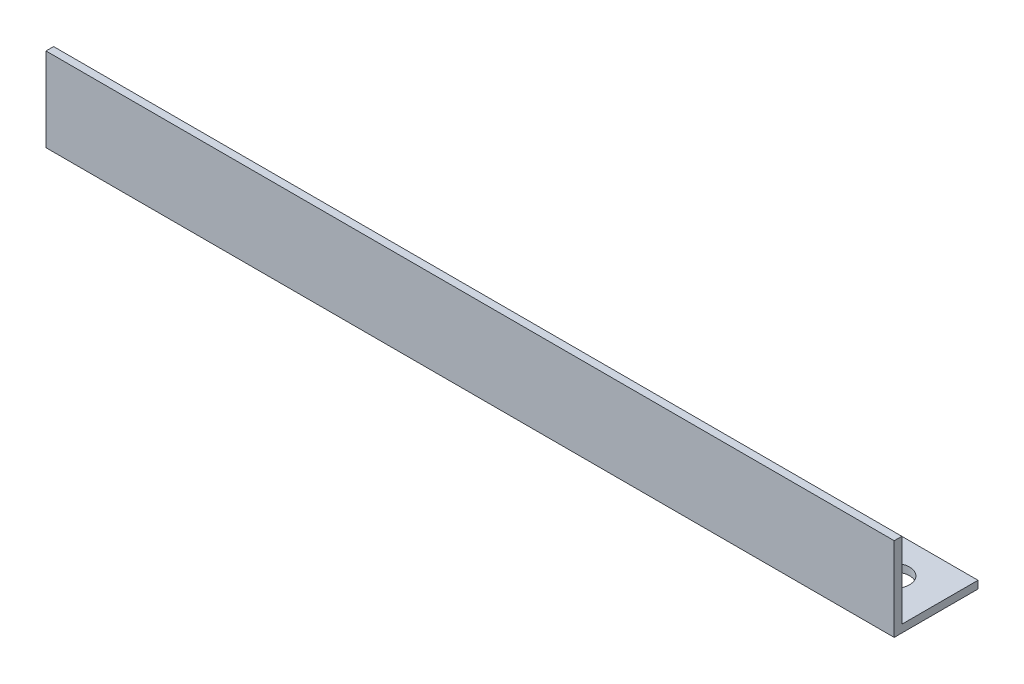
SolidWorks part; units mm, degrees
ref_plane "Спереди" through (0, 0, 0) normal (0, 0, 1) x (1, 0, 0)
ref_plane "Сверху" through (0, 0, 0) normal (0, 1, 0) x (1, 0, 0)
ref_plane "Справа" through (0, 0, 0) normal (1, 0, 0) x (0, 0, -1)
sketch "Эскиз1" plane through (0, 0, 0) normal (1, 0, 0) x (0, 0, -1)
  line L0 (0, 33) -> (0, 0)
  line L1 (0, 0) -> (33, 0)
extrude "Вытянуть-Тонкостенный1" add sketch "Эскиз1" along normal blind 334 thin thin type one direction reverse wall 3
sketch "Эскиз2" plane through (0, 0, 0) normal (0, -1, 0) x (1, 0, 0)
  line L0 (167, 0) -> (167, -50.3866) construction
  line L1 (334, 0) -> (0, 0) construction
  circle A0 centre (316, -18) radius 6.05
  circle A1 centre (18, -18) radius 6.05
extrude "Вырез-Вытянуть1" cut sketch "Эскиз2" against normal through all
